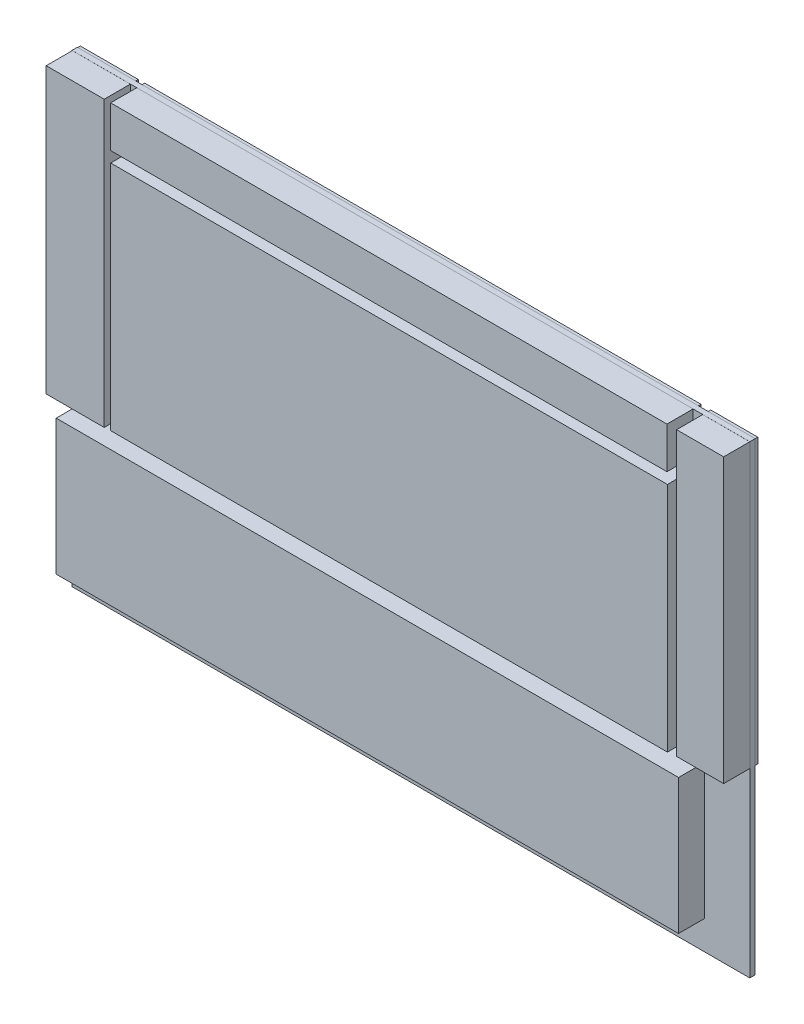
SolidWorks part; units mm, degrees
ref_plane "Front Plane" through (0, 0, 0) normal (0, 0, 1) x (1, 0, 0)
ref_plane "Top Plane" through (0, 0, 0) normal (0, 1, 0) x (1, 0, 0)
ref_plane "Right Plane" through (0, 0, 0) normal (1, 0, 0) x (0, 0, -1)
sketch "Sketch4" plane through (0, 0, 0) normal (0, 0, 1) x (1, 0, 0)
  line L0 (-124.8745, 31.4675) -> (197.9595, 31.4675)
  line L1 (-124.8745, 31.4675) -> (-124.8745, -189.7665)
  line L2 (197.9595, 31.4675) -> (197.9595, -189.7665)
  line L3 (-124.8745, -189.7665) -> (197.9595, -189.7665)
extrude "Boss-Extrude4" add sketch "Sketch4" along normal blind 2.54 contours L1 L3 L2 L0 | L2 L0 L1 L3 region at (36.5425, -79.1495, 0)
sketch "Sketch5" plane through (0, 0, 2.54) normal (0, 0, 1) x (1, 0, 0)
  line L21 (-119.973, -111.5629) -> (176.4698, -111.5629)
  line L22 (-119.973, -111.5629) -> (-119.973, -175.9387)
  line L23 (-119.973, -175.9387) -> (176.4698, -175.9387)
  line L24 (176.4698, -111.5629) -> (176.4698, -175.9387)
  line L25 (-94.0267, 31.4675) -> (170.9494, 31.4675) construction
  line L29 (197.9595, 31.4675) -> (197.9595, -189.7665) construction
  line L30 (197.9595, 31.44) -> (175.5464, 31.44)
  line L31 (197.9595, 31.44) -> (197.9595, -103.3511)
  line L32 (197.9595, -103.3511) -> (175.5464, -103.3511)
  line L33 (175.5464, 31.44) -> (175.5464, -103.3511)
  line L39 (-94.0267, 6.6547) -> (171.1692, 6.6547)
  line L40 (-94.0267, 6.6547) -> (-94.0267, -103.7582)
  line L41 (-94.0267, -103.7582) -> (171.1692, -103.7582)
  line L42 (171.1692, 6.6547) -> (171.1692, -103.7582)
  line L47 (-94.0267, 31.4675) -> (170.9494, 31.4675)
  line L48 (-94.0267, 31.4675) -> (-94.0267, 11.7821)
  line L49 (-94.0267, 11.7821) -> (170.9494, 11.7821)
  line L50 (170.9494, 31.4675) -> (170.9494, 11.7821)
  line L55 (-124.7216, 31.44) -> (-97.0975, 31.44)
  line L56 (-124.7216, 31.44) -> (-124.7216, -103.9677)
  line L57 (-124.7216, -103.9677) -> (-97.0975, -103.9677)
  line L58 (-97.0975, 31.44) -> (-97.0975, -103.9677)
  point P22 (164.1293, 13.788)
  point P23 (0, 0)
extrude "Boss-Extrude5" add sketch "Sketch5" along normal blind 12.446 and the other way blind 3.81
ref_plane "Plane1" through (176.4698, -175.9387, -1.27) normal (0, 1, 0) x (1, 0, 0)
